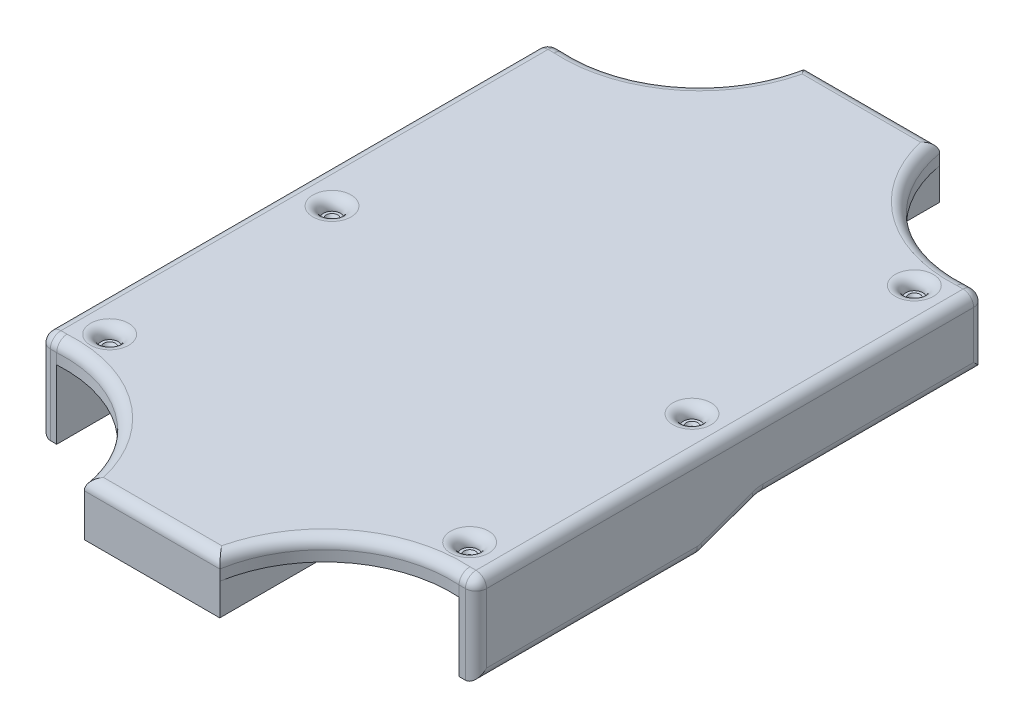
SolidWorks part; units mm, degrees
material "ABS"
ref_plane "Front" through (0, 0, 0) normal (0, 0, 1) x (1, 0, 0)
ref_plane "Top" through (0, 0, 0) normal (0, 1, 0) x (1, 0, 0)
ref_plane "Right" through (0, 0, 0) normal (1, 0, 0) x (0, 0, -1)
sketch "Sketch1" plane through (0, 0, 0) normal (0, 1, 0) x (1, 0, 0)
  line L0 (-20.32, 107.95) -> (20.32, 107.95)
  line L1 (-60.325, 76.2) -> (60.325, 76.2)
  line L2 (-60.325, 76.2) -> (-60.325, -76.2)
  line L3 (-60.325, -76.2) -> (60.325, -76.2)
  line L4 (60.325, 76.2) -> (60.325, -76.2)
  line L5 (-60.325, 76.2) -> (60.325, -76.2) construction
  line L6 (-60.325, -76.2) -> (60.325, 76.2) construction
  line L7 (-50, 0) -> (50, 0) construction
  line L8 (-20.32, -107.95) -> (20.32, -107.95)
  arc A0 (-60.325, 76.2) -> (-20.32, 107.95) centre (-57.9001, 114.2228) ccw
  arc A1 (20.32, 107.95) -> (60.325, 76.2) centre (57.9001, 114.2228) ccw
  arc A2 (20.32, -107.95) -> (60.325, -76.2) centre (57.9001, -114.2228) cw
  arc A3 (-60.325, -76.2) -> (-20.32, -107.95) centre (-57.9001, -114.2228) cw
  point P0 (0, 0)
  point P9 (0, 107.95)
  point P17 (0, -107.95)
  dimension "D5" = 38.1
  dimension "D1" = 120.65
  dimension "D2" = 152.4
  dimension "D3" = 40.64
  dimension "D4" = 31.75
extrude "Boss-Extrude1" add sketch "Sketch1" along normal blind 6.35 contours L4 L1 L2 L3 | L3 A3 L8 A2 | A1 L0 A0 L1 region at (0, 0, -89.6266) region at (0, 0, 0) region at (0, 0, 89.6266)
sketch "Sketch3" plane through (0, 0, 0) normal (0, -1, 0) x (1, 0, 0)
  line L1 (-20.32, 107.95) -> (20.32, 107.95)
  line L2 (-20.32, 107.95) -> (-20.32, 76.2)
  line L3 (-20.32, 76.2) -> (20.32, 76.2)
  line L4 (20.32, 107.95) -> (20.32, 76.2)
  line L5 (-20.32, -107.95) -> (20.32, -107.95)
  line L6 (-20.32, -107.95) -> (-20.32, -76.2)
  line L7 (-20.32, -76.2) -> (20.32, -76.2)
  line L8 (20.32, -107.95) -> (20.32, -76.2)
  point P11 (20.32, -107.95)
  dimension "D1" = 31.75
extrude "Boss-Extrude3" add sketch "Sketch3" along normal blind 9.525
sketch "Sketch2" plane through (60.325, 0, 0) normal (-1, 0, 0) x (0, 0, 1)
  line L0 (-76.2, 6.35) -> (76.2, 6.35)
  line L1 (76.2, 6.35) -> (76.2, -20.6375)
  line L2 (76.2, -20.6375) -> (8.7232, -20.6375)
  line L3 (8.7232, -20.6375) -> (-8.7232, -14.2875)
  line L4 (-8.7232, -14.2875) -> (-76.2, -14.2875)
  line L5 (-76.2, -14.2875) -> (-76.2, 6.35)
  line L6 (76.1228, 0) -> (107.95, 0) construction
  line L7 (-107.95, 0) -> (-76.1228, 0) construction
  point P15 (0, -17.4625)
  dimension "D1" = 20.6375
  dimension "D2" = 14.2875
  dimension "D3" = 200
extrude "Boss-Extrude2" add sketch "Sketch2" against normal blind 5.08
mirror "Mirror2" about plane through (0, 0, 0) normal (1, 0, 0) of "Boss-Extrude2"
sketch "Sketch4" plane through (0, 6.35, 0) normal (0, 1, 0) x (1, 0, 0)
  line L0 (-53.975, 0) -> (53.975, 0) construction
  line L1 (53.975, 0) -> (53.975, 66.675) construction
  line L2 (53.975, 0) -> (53.975, -66.675) construction
  circle A0 centre (-53.975, 0) radius 2.54
  circle A1 centre (53.975, 0) radius 2.54
  circle A2 centre (53.975, -66.675) radius 2.54
  circle A3 centre (53.975, 66.675) radius 2.54
  circle A4 centre (-53.975, -66.675) radius 2.54
  point P3 (-53.975, -57.2139)
  point P4 (0, 0)
  dimension "D3" = 5.08
  dimension "D1" = 107.95
  dimension "D2" = 66.675
extrude "Cut-Extrude1" cut sketch "Sketch4" against normal blind 3.175
hole_wizard "#2 Clearance Hole1" positions "Sketch5" profile "Sketch7" hole size "#2" standard "ANSI Inch" end condition through all
sketch "Sketch5" plane through (0, 3.175, 0) normal (0, 1, 0) x (1, 0, 0)
  point P0 (-53.975, 0)
  point P3 (53.975, 0)
  point P6 (53.975, 66.675)
  point P9 (53.975, -66.675)
  point P12 (-53.975, -66.675)
sketch "Sketch7" plane through (-53.975, 3.175, 0) normal (1, 0, 0) x (0, 0, 1)
  line L0 (0, 0) -> (0, 23.8125)
  line L1 (0, 23.8125) -> (1.0795, 23.8125)
  line L2 (1.0795, 23.8125) -> (1.0795, 0.8275)
  line L3 (1.0795, 0.8275) -> (1.7145, 0)
  line L5 (1.7145, 0) -> (0, 0)
  line L6 (-1.0795, 0.8275) -> (-1.7145, 0) construction
  line L11 (0, -6.35) -> (0, 107.95) construction
  dimension "Thru Hole Dia." = 2.159
  dimension "Thru Hole Depth" = 23.8125
  dimension "Near C'Sink Dia." = 3.429
  dimension "Near C'Sink Angle" = 75
sketch "Sketch8" plane through (-65.405, 0, 0) normal (-1, 0, 0) x (0, 0, 1)
  line L0 (-76.2, 6.35) -> (-76.2, -14.2875) construction
  line L1 (-107.95, 0) -> (-76.1228, 0) construction
  circle A0 centre (-14.097, -15.875) radius 7
  dimension "D1" = 14
  dimension "D2" = 62.103
  dimension "D3" = 15.875
extrude "Cut-Extrude2" cut sketch "Sketch8" against normal up to next
chamfer "Chamfer1" distance 6.35 angle 45 1 edges at (-65.405, -8.8809, -13.8097)
fillet "Fillet6" radius 3.175 17 edges at (-62.865, 6.35, 76.2) (-65.405, 6.35, 0) (-62.865, 6.35, -76.2) (-34.2149, 6.35, -84.3794) (34.2149, 6.35, -84.3794) (62.865, 6.35, -76.2) (65.405, 6.35, 0) (62.865, 6.35, 76.2) (34.2149, 6.35, 84.3794) (-34.2149, 6.35, 84.3794) (0, 6.35, 107.95) (0, 6.35, -107.95) (-53.975, 6.35, 2.54) (-53.975, 6.35, 69.215) (53.975, 6.35, -64.135) (53.975, 6.35, 69.215) (53.975, 6.35, 2.54)
fillet "Fillet8" radius 6.35 2 edges at (62.865, -20.6375, 8.7232) (62.865, -14.2875, -8.7232)
fillet "Fillet9" radius 3.175 17 edges at (-64.4751, 5.4201, -75.2701) (-64.4751, 5.4201, 75.2701) (64.4751, 5.4201, 75.2701) (64.4751, 5.4201, -75.2701) (-65.405, -20.6375, 42.4616) (-65.405, -18.9026, 3.9567) (-65.405, -14.2875, -51.7761) (-65.405, -5.5563, -76.2) (-65.405, -8.7312, 76.2) (65.405, -8.7312, 76.2) (65.405, -5.5563, -76.2) (65.405, -14.2875, -43.0215) (65.405, -14.384, -8.7403) (65.405, -17.4625, 0) (65.405, -20.541, 8.7403) (65.405, -20.6375, 43.0215) (-65.405, -2.6029, -12.6568)
sketch "Sketch9" plane through (-65.405, 0, 0) normal (-1, 0, 0) x (0, 0, 1)
  line L5 (-38.0289, -4.699) -> (-25.527, -4.699)
  line L6 (-38.0289, -4.699) -> (-38.0289, -15.875)
  line L7 (-38.0289, -15.875) -> (-25.527, -15.875)
  line L8 (-25.527, -4.699) -> (-25.527, -15.875)
  line L9 (-38.0289, -4.699) -> (-25.527, -15.875) construction
  line L10 (-38.0289, -15.875) -> (-25.527, -4.699) construction
  point P0 (-14.097, -15.875)
  point P1 (-31.7779, -10.287)
  point P6 (-31.43, -18.2868)
  dimension "D1" = 11.176
  dimension "D2" = 12.5019
  dimension "D3" = 11.43
extrude "Cut-Extrude3" cut sketch "Sketch9" against normal up to next
